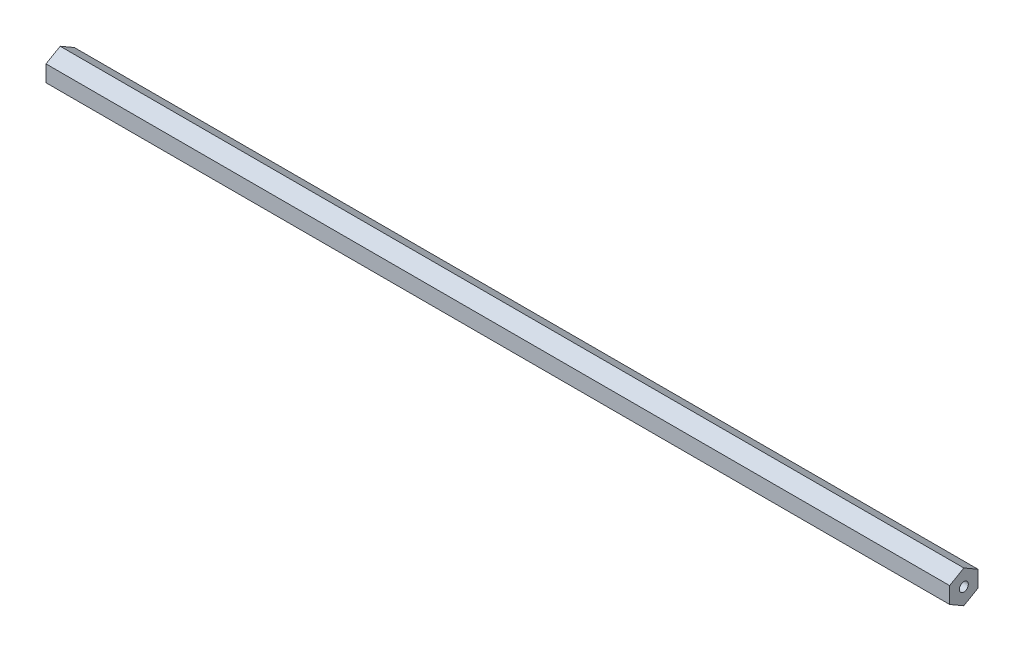
SolidWorks part; units mm, degrees
material "7075-T6 (SN)"
ref_plane "Front Plane" through (0, 0, 0) normal (0, 0, 1) x (1, 0, 0)
ref_plane "Top Plane" through (0, 0, 0) normal (0, 1, 0) x (1, 0, 0)
ref_plane "Right Plane" through (0, 0, 0) normal (1, 0, 0) x (0, 0, -1)
sketch "Sketch1" plane through (0, 0, 0) normal (1, 0, 0) x (0, 0, -1)
  line L1 (0, 7.3323) -> (-6.35, 3.6662)
  line L2 (-6.35, 3.6662) -> (-6.35, -3.6662)
  line L3 (-6.35, -3.6662) -> (0, -7.3323)
  line L4 (0, -7.3323) -> (6.35, -3.6662)
  line L5 (6.35, -3.6662) -> (6.35, 3.6662)
  line L6 (6.35, 3.6662) -> (0, 7.3323)
  circle A2 centre (0, 0) radius 6.35 construction
  dimension "D2" = 12.7
extrude "Boss-Extrude1" add sketch "Sketch1" along normal mid plane 404.8125 contours L5 L6 L1 L2 L3 L4 region at (0, 0, 0)
sketch "Sketch3" plane through (-200.8187, 0, 0) normal (-1, 0, 0) x (0, 0, 1)
  circle A0 centre (0, 0) radius 6.35
  dimension "D1" = 12.7
hole_wizard "#10-32 Tapped Hole1" positions "3DSketch1" profile "Sketch4" tap size "#10-32" standard "ANSI Inch"
sketch3d "3DSketch1"
  point P9 (202.4062, 0, 0)
  point P27 (-202.4062, 0, 0)
  point P30 (0, 0, 0)
sketch "Sketch4" plane through (202.4062, 0, 0) normal (0, 1, 0) x (0, 0, -1)
  line L0 (0, 0) -> (0, 17.5608)
  line L1 (0, 17.5608) -> (2.0193, 16.3474)
  line L2 (2.0193, 16.3474) -> (2.0193, 0)
  line L5 (2.0193, 0) -> (0, 0)
  line L10 (0, 17.5608) -> (-2.0193, 16.3474) construction
  line L11 (0, -6.35) -> (0, 107.95) construction
  dimension "Tap Drill Dia." = 4.0386
  dimension "Tap Drill Depth" = 16.3474
  dimension "Drill Angle" = 118
cosmetic thread "Hole Thread2"
cosmetic thread "Hole Thread3"
